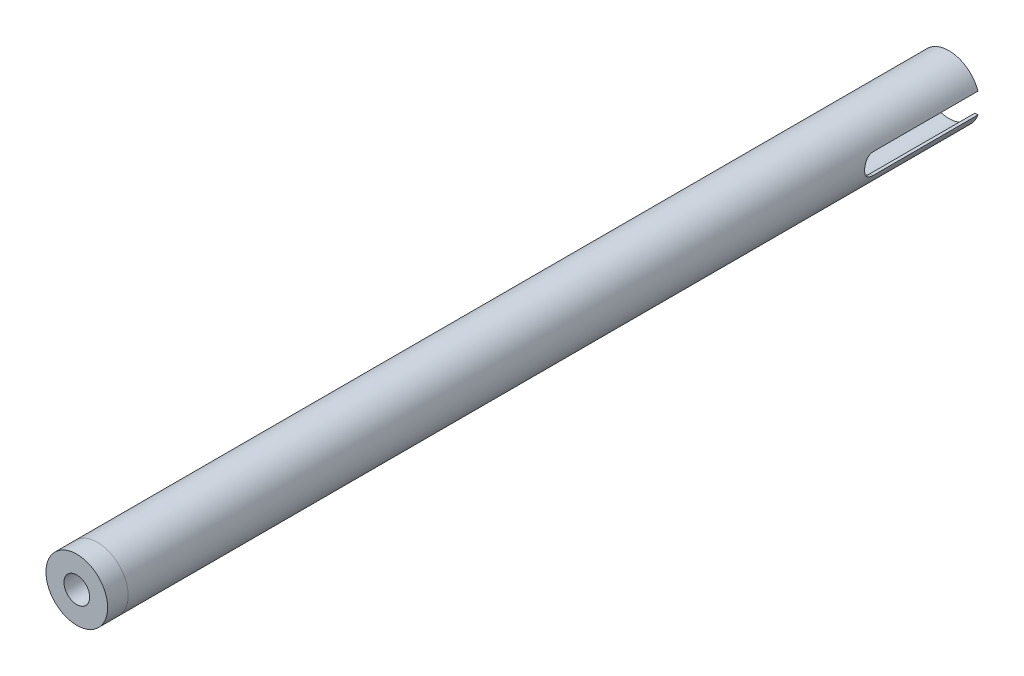
SolidWorks part; units mm, degrees
material "AISI 4130 Steel, annealed at 865C"
ref_plane "Front Plane" through (0, 0, 0) normal (0, 0, 1) x (1, 0, 0)
ref_plane "Top Plane" through (0, 0, 0) normal (0, 1, 0) x (1, 0, 0)
ref_plane "Right Plane" through (0, 0, 0) normal (1, 0, 0) x (0, 0, -1)
sketch "Axis" plane through (0, 0, 0) normal (0, 1, 0) x (1, 0, 0)
  line L0 (0, 0) -> (0, 269.3139) construction
  line L1 (0, 0) -> (0, -28.575) construction
  line L2 (0, 269.3139) -> (-9.525, 269.3139) construction
  line L3 (0, 294.3429) -> (-10.414, 266.9778) construction
  dimension "D1" = 28.575
  dimension "D2" = 9.525
sketch "Sketch1" plane through (0, 0, 0) normal (0, 0, 1) x (1, 0, 0)
  line L0 (-9.525, 0) -> (9.525, 0) construction
  line L1 (-8.9803, 3.175) -> (8.9803, 3.175)
  line L2 (-8.9803, -3.175) -> (8.9803, -3.175)
  circle A0 centre (0, 0) radius 9.525
  circle A1 centre (0, 0) radius 8.636
  circle A2 centre (0, 0) radius 3.9688
  dimension "D1" = 19.05
  dimension "D3" = 7.9375
  dimension "D2" = 0.889
  dimension "D4" = 6.35
extrude "Threaded insert 1-1" add sketch "Sketch1" against normal blind 6.35 contours A2 L1 A1 | A1 L1 A0 | A2 L0 A1 L1 | A1 L0 A0 L1 | L0 A1 L2 A0 | L0 A2 L2 A1 | A2 L2 A1 | A1 L2 A0 | L0 A1 L2 A2 | L0 A0 L2 A1 | A0 L0 A1 L1 | A1 L0 A2 L1 region at (5.9465, 1.6355, 0) region at (5.9465, -1.6355, 0) region at (8.8881, 1.6046, 0) region at (8.8881, -1.6046, 0) region at (-5.9465, -1.6355, 0) region at (-5.9465, 1.6355, 0) region at (0, 5.5139, 0) region at (0, -5.5139, 0) region at (0, 8.8265, 0) region at (8.5057, -3.3655, 0) region at (-8.8881, -1.6046, 0) region at (-8.8881, 1.6046, 0)
extrude "Threaded insert 1-2" add sketch "Sketch1<3>" against normal blind 9.525 from surface contours A2 L1 A1 | A2 L0 A1 L1 | L0 A2 L2 A1 | A2 L2 A1 | L0 A1 L2 A2 | A1 L0 A2 L1 region at (5.9465, 1.6355, 0) region at (5.9465, -1.6355, 0) region at (-5.9465, -1.6355, 0) region at (-5.9465, 1.6355, 0) region at (0, 5.5139, 0) region at (0, -5.5139, 0) starting at face at (9.525, 0, -6.35)
sketch "Sketch1<3>" plane through (0, 0, 0) normal (0, 0, 1) x (1, 0, 0) same geometry as "Sketch1"
extrude "A-arm tube" add sketch "Sketch1<4>" against normal up to vertex (269.3139 mm away) from surface separate body contours A1 L1 A0 | A1 L0 A0 L1 | L0 A1 L2 A0 | A1 L2 A0 | L0 A0 L2 A1 | A0 L0 A1 L1 region at (8.8881, 1.6046, 0) region at (8.8881, -1.6046, 0) region at (0, 8.8265, 0) region at (8.5057, -3.3655, 0) region at (-8.8881, -1.6046, 0) region at (-8.8881, 1.6046, 0) up to point (0, 0, -269.3139) starting at face at (8.636, 0, -6.35)
sketch "Sketch1<4>" plane through (0, 0, 0) normal (0, 0, 1) x (1, 0, 0) same geometry as "Sketch1"
extrude "Apex slot" cut sketch "Sketch1<5>" along normal blind 35.56 from surface contours A0 L0 A1 L1 | L0 A0 L2 A1 | A1 L0 A0 L1 | L0 A1 L2 A0 region at (8.8881, 1.6046, 0) region at (8.8881, -1.6046, 0) region at (-8.8881, -1.6046, 0) region at (-8.8881, 1.6046, 0) starting at face at (8.636, 0, -269.3139)
sketch "Sketch1<5>" plane through (0, 0, 0) normal (0, 0, 1) x (1, 0, 0) same geometry as "Sketch1"
fillet "Fillet1" radius 3.175 4 edges at (-8.5057, 3.175, -233.7539) (-8.5057, -3.175, -233.7539) (8.5057, -3.175, -233.7539) (8.5057, 3.175, -233.7539)
equation "\"tube diameter\"= 3 / 4"
equation "\"tube thickness\"= .035"
equation "\"apex thickness\"= .25"
equation "\"tube slot\"= 1.4"
equation "\"D1@Sketch1\"=\"tube diameter\""
equation "\"D2@Sketch1\"=\"tube thickness\""
equation "\"threaded insert hole\"= .3125"
equation "\"D3@Sketch1\"=\"threaded insert hole\""
equation "\"D4@Sketch1\"=\"apex thickness\""
equation "\"D1@Apex slot\" = \"tube slot\""
equation "\"D1@Fillet1\"=\"apex thickness\"/2"
equation "\"D2@Axis\"=\"tube diameter\"/2"
